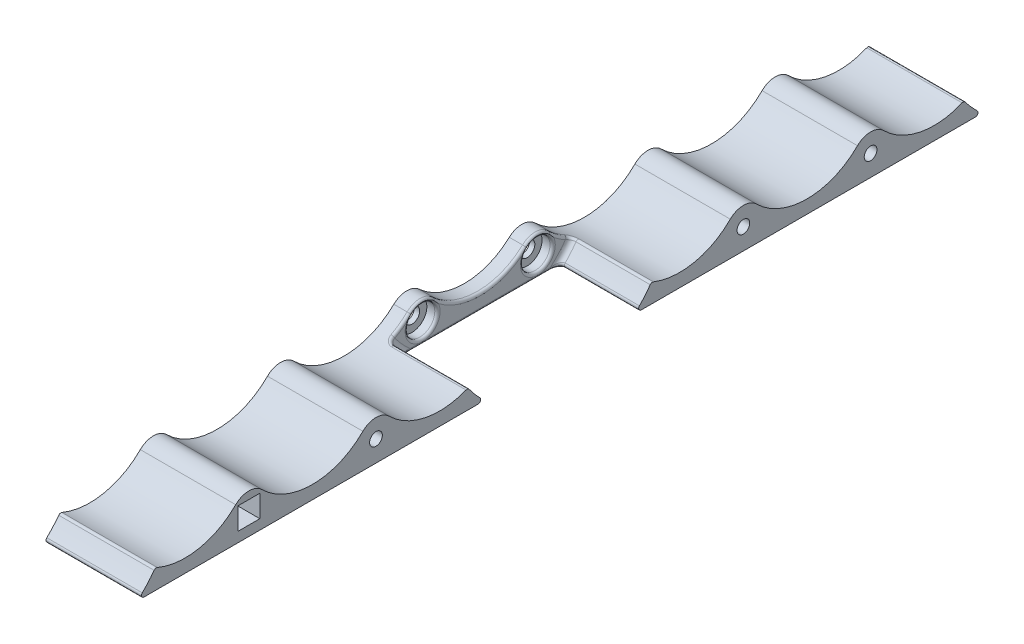
SolidWorks part; units mm, degrees
ref_plane "Front Plane" through (0, 0, 0) normal (0, 0, 1) x (1, 0, 0)
ref_plane "Top Plane" through (0, 0, 0) normal (0, 1, 0) x (1, 0, 0)
ref_plane "Right Plane" through (0, 0, 0) normal (1, 0, 0) x (0, 0, -1)
sketch "Sketch1" plane through (0, 0, 0) normal (1, 0, 0) x (0, 0, -1)
  line L0 (-126.5656, -24.6062) -> (126.5656, -24.6062)
  arc A0 (126.5656, -24.6062) -> (121.1052, -18.6881) centre (148.1579, 0.7938) cw
  arc A1 (-126.5656, -24.6062) -> (-121.1052, -18.6881) centre (-148.1579, 0.7937) ccw
  circle A2 centre (-93.1246, -18.3223) radius 5.5562 construction
  arc A3 (-93.1246, -9.0244) -> (-55.0246, -9.0244) centre (-74.0746, 0.7938) ccw construction
  circle A4 centre (-55.0246, -18.3223) radius 5.5562 construction
  arc A5 (-55.0246, -9.0244) -> (-17.2998, -9.7206) centre (-35.9746, 0.7938) ccw construction
  circle A6 centre (-17.2515, -18.6426) radius 5.5562 construction
  arc A7 (-17.2998, -9.7206) -> (17.2998, -9.7206) centre (0, 0) ccw construction
  circle A8 centre (17.2515, -18.6426) radius 5.5562 construction
  arc A9 (17.2998, -9.7206) -> (55.0246, -9.0244) centre (35.9746, 0.7937) ccw construction
  circle A10 centre (55.0246, -18.3223) radius 5.5562 construction
  circle A11 centre (93.1246, -18.3223) radius 5.5562 construction
  arc A12 (93.1246, -9.0244) -> (131.0767, -9.3061) centre (112.1746, 0.7937) ccw construction
  arc A13 (55.0246, -9.0244) -> (93.1246, -9.0244) centre (74.0746, 0.7937) ccw construction
  arc A14 (-89.2025, -14.3866) -> (-97.0466, -14.3866) centre (-93.1246, -18.3223) ccw
  arc A15 (-89.2025, -14.3866) -> (-58.9466, -14.3866) centre (-74.0746, 0.7938) ccw
  arc A16 (-51.1025, -14.3866) -> (-58.9466, -14.3866) centre (-55.0246, -18.3223) ccw
  arc A17 (-51.1025, -14.3866) -> (-21.1062, -14.641) centre (-35.9746, 0.7938) ccw
  arc A18 (-13.4777, -14.5645) -> (-21.1062, -14.641) centre (-17.2515, -18.6426) ccw
  arc A19 (-13.4777, -14.5645) -> (13.4777, -14.5645) centre (0, 0) ccw
  arc A20 (21.1062, -14.641) -> (13.4777, -14.5645) centre (17.2515, -18.6426) ccw
  arc A21 (21.1062, -14.641) -> (51.1025, -14.3866) centre (35.9746, 0.7937) ccw
  arc A22 (58.9466, -14.3866) -> (51.1025, -14.3866) centre (55.0246, -18.3223) ccw
  arc A23 (97.0466, -14.3866) -> (89.2025, -14.3866) centre (93.1246, -18.3223) ccw
  arc A24 (97.0466, -14.3866) -> (121.1052, -18.6881) centre (112.1746, 0.7937) ccw
  arc A25 (58.9466, -14.3866) -> (89.2025, -14.3866) centre (74.0746, 0.7937) ccw
  arc A26 (-131.0767, -9.3061) -> (-93.1246, -9.0244) centre (-112.1746, 0.7937) ccw construction
  arc A27 (-121.1052, -18.6881) -> (-97.0466, -14.3866) centre (-112.1746, 0.7937) ccw
  arc A28 (-125.2787, 25.041) -> (-169.3185, 26.5545) centre (-148.1579, 0.7937) ccw construction
  circle A29 centre (148.1579, 0.7938) radius 2.032 construction
  point P3 (0, -24.6062)
  dimension "D1" = 24.6062
extrude "Boss-Extrude1" add sketch "Sketch1" along normal up to surface (28.575 mm away)
sketch "Sketch2" plane through (28.575, 0, 0) normal (1, 0, 0) x (0, 0, -1)
  circle A0 centre (0, 0) radius 33.3375
  dimension "D1" = 66.675
extrude "Cut-Extrude1" cut sketch "Sketch2" against normal blind 23.8125
sketch "Sketch3" plane through (28.575, 0, 0) normal (1, 0, 0) x (0, 0, -1)
  line L9 (-89.8226, -15.0203) -> (-96.4266, -15.0203)
  line L10 (-89.8226, -21.6243) -> (-89.8226, -15.0203)
  line L11 (-96.4266, -21.6243) -> (-89.8226, -21.6243)
  line L12 (-96.4266, -15.0203) -> (-96.4266, -21.6243)
  line L13 (-89.8226, -15.0203) -> (-96.4266, -15.0203)
  line L14 (-89.8226, -21.6243) -> (-89.8226, -15.0203)
  line L15 (-96.4266, -21.6243) -> (-89.8226, -21.6243)
  line L16 (-96.4266, -15.0203) -> (-96.4266, -21.6243)
  dimension "D1" = 0.127
extrude "Cut-Extrude2" cut sketch "Sketch3" against normal through all
sketch "Sketch4" plane through (28.575, 0, 0) normal (1, 0, 0) x (0, 0, -1)
  circle A0 centre (93.1246, -18.3223) radius 2.032 construction
  point P0 (-55.0246, -18.3223)
  point P3 (55.0246, -18.3223)
  point P6 (93.1246, -18.3223)
hole_wizard "#8 Clearance Hole1" positions "Sketch4" profile "Sketch5" hole size "#8" standard "ANSI Inch" end condition up to next
sketch "Sketch5" plane through (28.575, -18.3223, 55.0246) normal (0, 1, 0) x (0, 0, -1)
  line L0 (0, 0) -> (0, 28.575)
  line L1 (0, 28.575) -> (1.905, 28.575)
  line L2 (1.905, 28.575) -> (1.905, 0)
  line L5 (1.905, 0) -> (0, 0)
  line L11 (0, -6.35) -> (0, 107.95) construction
  dimension "Thru Hole Dia." = 3.81
  dimension "Thru Hole Depth" = 28.575
sketch "Sketch6" plane through (4.7625, 0, 0) normal (1, 0, 0) x (0, 0, -1)
  circle A0 centre (-17.2515, -18.6426) radius 4.445
  circle A1 centre (17.2515, -18.6426) radius 4.445
  dimension "D1" = 8.89
extrude "Cut-Extrude3" cut sketch "Sketch6" against normal blind 3.175
sketch "Sketch7" plane through (1.5875, 0, 0) normal (1, 0, 0) x (0, 0, -1)
  point P0 (-17.2515, -18.6426)
  point P3 (17.2515, -18.6426)
hole_wizard "#8 Clearance Hole2" positions "Sketch7" profile "Sketch8" hole size "#8" standard "ANSI Inch" end condition up to next
sketch "Sketch8" plane through (1.5875, -18.6426, 17.2515) normal (0, 1, 0) x (0, 0, -1)
  line L0 (0, 0) -> (0, 1.5875)
  line L1 (0, 1.5875) -> (2.286, 1.5875)
  line L2 (2.286, 1.5875) -> (2.286, 0)
  line L5 (2.286, 0) -> (0, 0)
  line L11 (0, -6.35) -> (0, 107.95) construction
  dimension "Thru Hole Dia." = 4.572
  dimension "Thru Hole Depth" = 1.5875
fillet "Fillet1" radius 1.5875 2 edges at (4.7625, -21.8856, -25.1478) (4.7625, -21.8856, 25.1478)
fillet "Fillet2" radius 0.7937 20 edges at (17.4625, -18.8803, -27.4758) (5.116, -18.6353, -26.9296) (4.7625, -16.5891, -23.4393) (4.7625, -13.0866, -17.3072) (17.4625, -18.8803, 27.4758) (5.3711, -18.7415, 27.1614) (4.7625, -16.5891, 23.4393) (4.7625, -13.0866, 17.3072) (17.4625, -24.6062, 22.4927) (5.2999, -24.6062, 21.9001) (17.4625, -24.6062, -22.4927) (5.5963, -24.6062, -22.2096) (4.7625, -18.6426, -21.6965) (4.7625, -18.6426, 12.8065) (4.7625, -19.8437, 0) (4.7625, -24.6062, 0) (14.2875, -24.6062, -126.5656) (14.2875, -18.6881, -121.1052) (14.2875, -24.6062, 126.5656) (14.2875, -18.6881, 121.1052)
